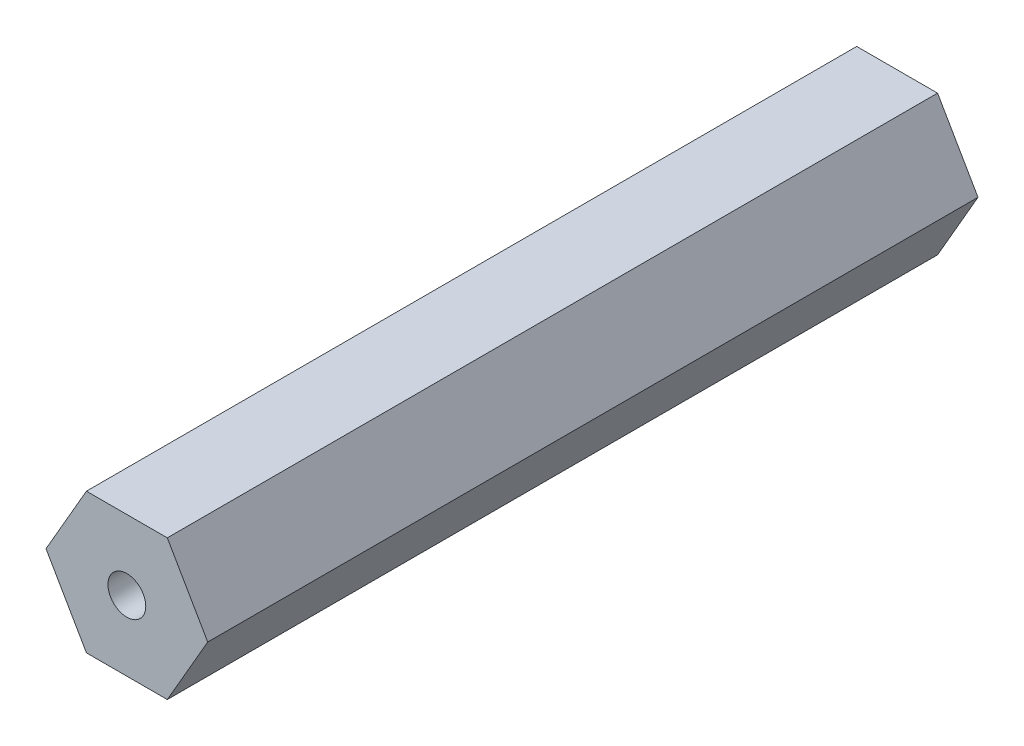
SolidWorks part; units mm, degrees
material "7075-T6 (SN)"
ref_plane "Front Plane" through (0, 0, 0) normal (0, 0, 1) x (1, 0, 0)
ref_plane "Top Plane" through (0, 0, 0) normal (0, 1, 0) x (1, 0, 0)
ref_plane "Right Plane" through (0, 0, 0) normal (1, 0, 0) x (0, 0, -1)
other "Configuration Table"
sketch "Sketch1" plane through (0, 0, 0) normal (0, 0, 1) x (1, 0, 0)
  line L1 (7.3323, 0) -> (3.6662, 6.35)
  line L2 (3.6662, 6.35) -> (-3.6662, 6.35)
  line L3 (-3.6662, 6.35) -> (-7.3323, 0)
  line L4 (-7.3323, 0) -> (-3.6662, -6.35)
  line L5 (-3.6662, -6.35) -> (3.6662, -6.35)
  line L6 (3.6662, -6.35) -> (7.3323, 0)
  circle A0 centre (0, 0) radius 6.35 construction
  circle A1 centre (0, 0) radius 1.7145
  dimension "D2" = 3.429
  dimension "D1" = 12.7
extrude "Boss-Extrude1" add sketch "Sketch1" along normal mid plane 69.85
fillet "Fillet1" [suppressed] radius 0.635
equation "\"length\"= 2.75"
equation "\"D1@Boss-Extrude1\"=\"length\""
